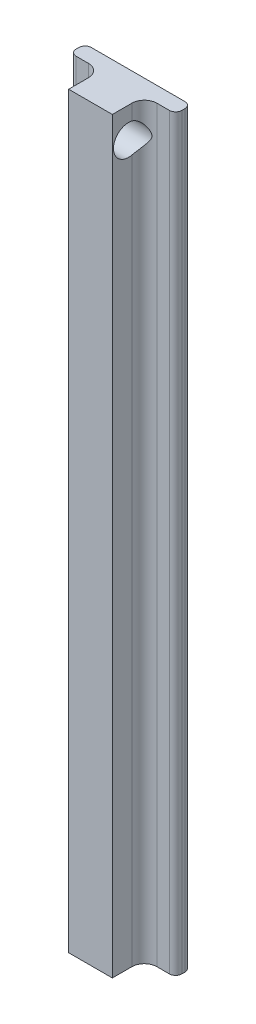
SolidWorks part; units mm, degrees
ref_plane "Front Plane" through (0, 0, 0) normal (0, 0, 1) x (1, 0, 0)
ref_plane "Top Plane" through (0, 0, 0) normal (0, 1, 0) x (1, 0, 0)
ref_plane "Right Plane" through (0, 0, 0) normal (1, 0, 0) x (0, 0, -1)
sketch "Sketch1" plane through (0, 0, 0) normal (0, 1, 0) x (1, 0, 0)
  line L0 (0, 0) -> (-21.5958, 0)
  line L1 (-21.5958, 0) -> (-21.5958, -9.6732)
  line L2 (-21.5958, -9.6732) -> (0, -9.6732)
  line L3 (0, -9.6732) -> (0, 0)
extrude "Boss-Extrude1" add sketch "Sketch1" along normal blind 152.4 contours L3 L0 L1 L2
sketch "Sketch2" plane through (0, 152.4, 0) normal (0, 1, 0) x (1, 0, 0)
  line L0 (-21.5958, -9.6732) -> (-15.2732, -9.6732)
  line L1 (-21.5958, -9.6732) -> (0, -9.6732) construction
  line L2 (-15.2732, -9.6732) -> (-15.2732, -3.0901)
  line L3 (-15.2732, -3.0901) -> (-21.5958, -3.0901)
  line L4 (-21.5958, 0) -> (-21.5958, -9.6732) construction
  line L5 (-21.5958, -3.0901) -> (-21.5958, -9.6732)
extrude "Cut-Extrude1" cut sketch "Sketch2" against normal blind 169.418 contours L5 L0 L2 L3
sketch "Sketch3" plane through (0, 152.4, 0) normal (0, 1, 0) x (1, 0, 0)
  line L0 (0, -9.6732) -> (-6.3637, -9.6732)
  line L1 (-15.2732, -9.6732) -> (0, -9.6732) construction
  line L2 (-6.3637, -9.6732) -> (-6.3637, -3.1444)
  line L3 (-6.3637, -3.1444) -> (0, -3.1444)
  line L4 (0, -9.6732) -> (0, 0) construction
  line L5 (0, -3.1444) -> (0, -9.6732)
extrude "Cut-Extrude2" cut sketch "Sketch3" against normal blind 184.912 contours L5 L0 L2 L3
fillet "Fillet2" radius 1.27 1 edges at (-21.5958, 76.2, 3.0901)
fillet "Fillet3" radius 1.27 1 edges at (-21.5958, 76.2, 0)
fillet "Fillet4" radius 1.27 1 edges at (0, 76.2, 0)
fillet "Fillet5" radius 2.54 1 edges at (-6.3637, 76.2, 3.1444)
fillet "Fillet6" radius 1.27 1 edges at (0, 76.2, 3.1444)
sketch "Sketch5" plane through (-15.2732, 0, 0) normal (-1, 0, 0) x (0, 0, 1)
  circle A1 centre (6.3645, 146.251) radius 3.0758
extrude "Cut-Extrude4" cut sketch "Sketch5" against normal blind 27.0848 contours A1
fillet "Fillet7" radius 2.54 1 edges at (-15.2732, 76.2, 3.0901)
